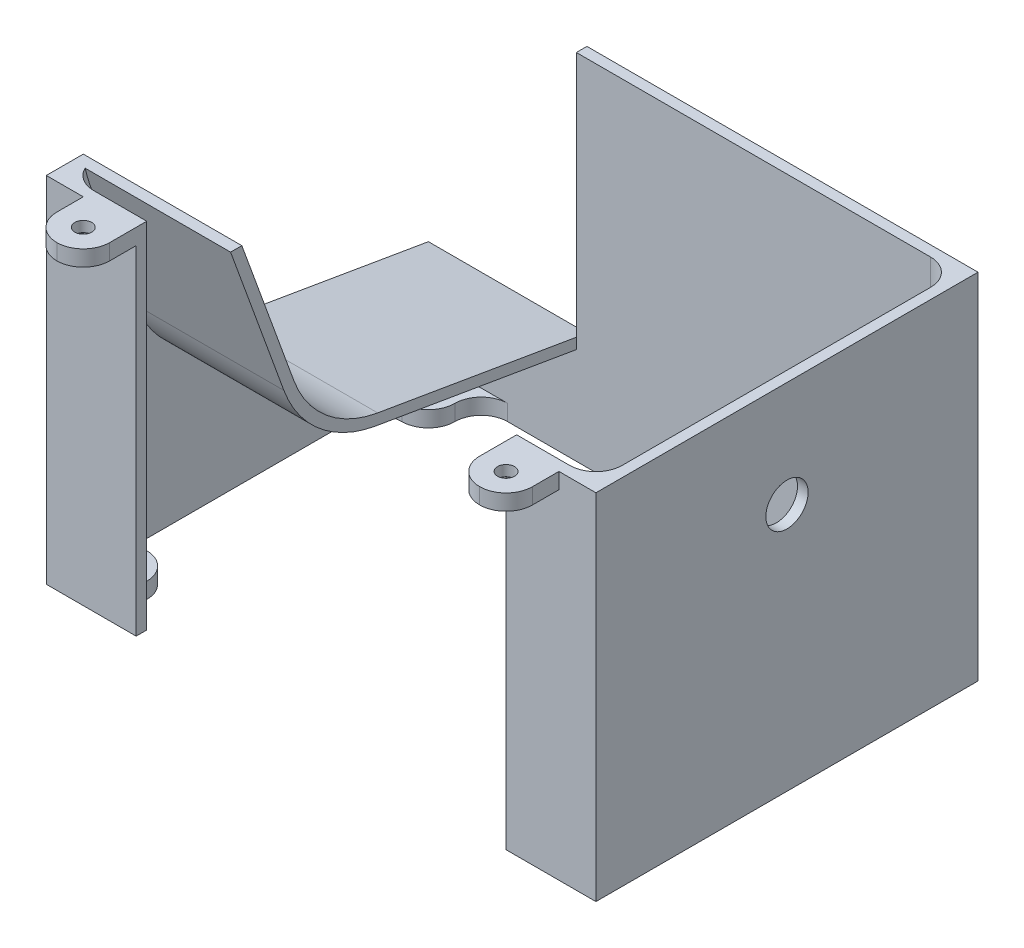
SolidWorks part; units mm, degrees
ref_plane "Front Plane" through (0, 0, 0) normal (0, 0, 1) x (1, 0, 0)
ref_plane "Top Plane" through (0, 0, 0) normal (0, 1, 0) x (1, 0, 0)
ref_plane "Right Plane" through (0, 0, 0) normal (1, 0, 0) x (0, 0, -1)
sketch "Sketch1" plane through (0, 0, 0) normal (0, 1, 0) x (1, 0, 0)
  line L0 (-7, -7) -> (45, -7)
  line L1 (0, -5) -> (45, -5)
  line L2 (-7, -7) -> (-7, 29.15)
  line L3 (-5, 0) -> (-5, 29.15)
  line L34 (45, -5) -> (45, -7)
  line L35 (-7, 29.15) -> (-5, 29.15)
  arc A0 (-5, 0) -> (0, -5) centre (0, 0) ccw
  circle A1 centre (0, 0) radius 1.6
  arc A3 (5, 0) -> (10, -5) centre (10, 0) ccw
  arc A4 (-5, 10) -> (0, 5) centre (0, 10) ccw
  arc A5 (5, 0) -> (0, 5) centre (0, 0) ccw
  point P7 (-7, -7)
  point P8 (-6.5937, -7)
  dimension "D1" = 3.2
  dimension "D2" = 10
  dimension "D4" = 5
  dimension "D5" = 5
  dimension "D6" = 5
  dimension "D7" = 5
  dimension "D8" = 45
  dimension "D9" = 2
  dimension "D10" = 2
  dimension "D11" = 29.15
extrude "Boss-Extrude1" add sketch "Sketch1" against normal blind 3 contours A3 A5 A4 L3 A0 L1 A1 | L2 L0 L1 A0 L3 L35 region at (-6.3667, 0, -11.075) region at (5, 0, 4.7879)
extrude "Boss-Extrude2" add sketch "Sketch1<3>" along normal blind 32 contours L2 L0 L1 A0 L3 L35 region at (-6.3667, 0, -11.075)
sketch "Sketch1<3>" plane through (0, 0, 0) normal (0, 1, 0) x (1, 0, 0) same geometry as "Sketch1"
ref_plane "Plane1" through (0, 32, 0) normal (0, 1, 0) x (1, 0, 0)
mirror "Mirror2" about plane through (0, 32, 0) normal (0, 1, 0) of "Boss-Extrude2"
mirror "Mirror4" about plane through (45, -3, 0) normal (-1, 0, 0) of bodies 104 105
mirror "Mirror5" about plane through (90, -3, -29.15) normal (0, 0, 1) of bodies 106
ref_plane "Plane2" through (0, 0, -29.15) normal (0, 0, -1) x (-1, 0, 0)
sketch "Sketch2" plane through (0, 0, 7) normal (0, 0, 1) x (1, 0, 0)
  line L0 (-7, 64) -> (97, 64) construction
  line L1 (10, 64) -> (10, -3)
  line L2 (-7, -3) -> (97, -3) construction
  line L3 (10, -3) -> (80, -3)
  line L4 (80, -3) -> (80, 64)
  line L5 (80, 64) -> (10, 64)
  line L8 (-7, -3) -> (-7, 64) construction
  line L9 (97, -3) -> (97, 64) construction
  point P8 (0, 0)
  point P10 (77.5937, -3)
  point P11 (76.6256, -3)
  dimension "D1" = 17
  dimension "D2" = 17
extrude "Cut-Extrude1" cut sketch "Sketch2" against normal up to surface (2 mm away) up to face at (45, 15.25, 5)
sketch "Sketch10" plane through (0, 64, 0) normal (0, 1, 0) x (1, 0, 0)
  line L0 (0, -7) -> (10, -7)
  line L1 (0, -7) -> (0, -17)
  line L2 (10, -7) -> (10, -17)
  line L3 (0, -17) -> (10, -17)
  line L4 (90, -7) -> (80, -7)
  line L5 (90, -7) -> (90, -17)
  line L6 (80, -7) -> (80, -17)
  line L7 (90, -17) -> (80, -17)
  line L8 (0, -7) -> (10, -17) construction
  line L9 (80, -7) -> (90, -17) construction
  circle A0 centre (5, -12) radius 1.6
  circle A1 centre (85, -12) radius 1.6
  point P16 (0, 0)
  point P19 (0, 0)
  dimension "D1" = 3.2
  dimension "D2" = 10
extrude "Boss-Extrude3" add sketch "Sketch10" against normal blind 3
fillet "Fillet1" radius 5 4 edges at (0, 62.5, 17) (10, 62.5, 17) (90, 62.5, 17) (80, 62.5, 17)
sketch "Sketch11" plane through (0, 61, 0) normal (0, -1, 0) x (1, 0, 0)
  line L1 (8.2909, 12) -> (6.6454, 14.85)
  line L2 (6.6454, 14.85) -> (3.3546, 14.85)
  line L3 (3.3546, 14.85) -> (1.7091, 12)
  line L4 (1.7091, 12) -> (3.3546, 9.15)
  line L5 (3.3546, 9.15) -> (6.6454, 9.15)
  line L6 (6.6454, 9.15) -> (8.2909, 12)
  line L7 (88.2909, 12) -> (86.6454, 14.85)
  line L8 (86.6454, 14.85) -> (83.3546, 14.85)
  line L9 (83.3546, 14.85) -> (81.7091, 12)
  line L10 (81.7091, 12) -> (83.3546, 9.15)
  line L11 (83.3546, 9.15) -> (86.6454, 9.15)
  line L12 (86.6454, 9.15) -> (88.2909, 12)
  circle A0 centre (5, 12) radius 2.85 construction
  circle A1 centre (85, 12) radius 2.85 construction
  dimension "D1" = 5.7
extrude "Cut-Extrude5" cut sketch "Sketch11" against normal blind 1
sketch "Sketch4" plane through (-7, 0, 0) normal (-1, 0, 0) x (0, 0, 1)
  line L0 (7, 64) -> (-65.3, 64) construction
  circle A0 centre (-29.15, 44) radius 4
  point P6 (-35.6278, 44.042)
  dimension "D1" = 8
  dimension "D2" = 20
  dimension "D3" = 29.15
extrude "Cut-Extrude2" cut sketch "Sketch4" against normal through all
sketch "Sketch12" plane through (-7, 0, 0) normal (-1, 0, 0) x (0, 0, 1)
  line L0 (0, 64) -> (-9.8378, 36.9709)
  line L1 (-25.7017, 23.7397) -> (-65.3, 17)
  line L2 (0, 64) -> (-65.3, 64)
  line L3 (7, -3) -> (-65.3, -3) construction
  line L4 (7, -3) -> (7, 64) construction
  line L5 (7, 64) -> (-65.3, 64) construction
  line L6 (-65.3, -3) -> (-65.3, 64) construction
  line L7 (-65.3, 64) -> (-65.3, 17)
  arc A0 (-9.8378, 36.9709) -> (-25.7017, 23.7397) centre (-29.15, 44) cw
  point P6 (0, 0)
  point P9 (0, 0)
  point P11 (0, 0)
  point P16 (0, 0)
  dimension "D1" = 20
  dimension "D2" = 7
  dimension "D3" = 70
extrude "Cut-Extrude6" cut sketch "Sketch12" against normal blind 30
sketch "Sketch13" plane through (-5, 0, 0) normal (1, 0, 0) x (0, 0, -1)
  line L4 (65.3, 17) -> (63.3, 17.3404) construction
  line L5 (63.3, 17.3404) -> (58.3, 18.1914) construction
  line L6 (25.7017, 23.7397) -> (58.3, 18.1914) construction
  line L7 (0, 64) -> (9.8378, 36.9709) construction
  line L8 (65.3, 17) -> (63.3, 17.3404)
  line L9 (63.3, 17.3404) -> (58.3, 18.1914)
  line L10 (25.7017, 23.7397) -> (58.3, 18.1914)
  line L11 (0, 64) -> (9.8378, 36.9709)
  line L12 (65.3, 14.9712) -> (62.9644, 15.3688)
  line L13 (62.9644, 15.3688) -> (57.9644, 16.2198)
  line L14 (25.3661, 21.7681) -> (57.9644, 16.2198)
  line L15 (-2.1284, 64) -> (7.9584, 36.2869)
  line L16 (64.9644, 15.0284) -> (62.9644, 15.3688) construction
  line L17 (-1.8794, 63.316) -> (7.9584, 36.2869) construction
  line L18 (65.3, 17) -> (65.3, 14.9712)
  line L19 (-2.1284, 64) -> (0, 64)
  line L20 (65.3, -3) -> (65.3, 17) construction
  line L22 (-7, 64) -> (0, 64) construction
  arc A1 (9.8378, 36.9709) -> (25.7017, 23.7397) centre (29.15, 44) ccw construction
  arc A2 (9.8378, 36.9709) -> (25.7017, 23.7397) centre (29.15, 44) ccw
  arc A3 (7.9584, 36.2869) -> (25.3661, 21.7681) centre (29.15, 44) ccw
  dimension "D1" = 2
extrude "Boss-Extrude4" add sketch "Sketch13" along normal blind 28
